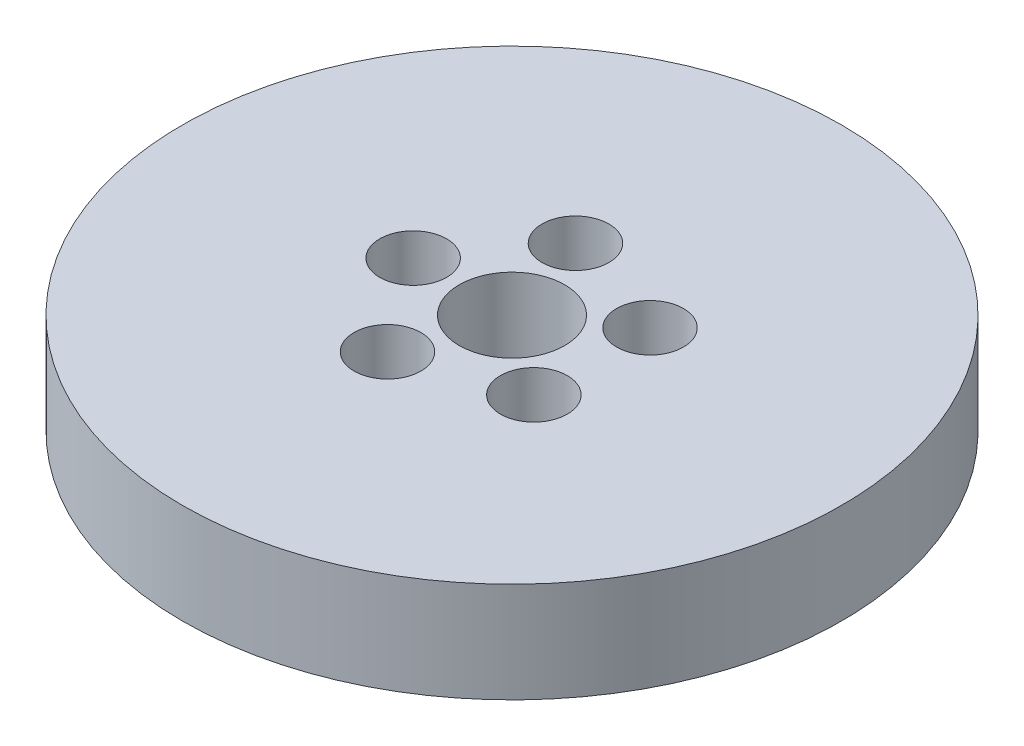
SolidWorks part; units mm, degrees
ref_plane "Front Plane" through (0, 0, 0) normal (0, 0, 1) x (1, 0, 0)
ref_plane "Top Plane" through (0, 0, 0) normal (0, 1, 0) x (1, 0, 0)
ref_plane "Right Plane" through (0, 0, 0) normal (1, 0, 0) x (0, 0, -1)
sketch "Sketch1" plane through (0, 0, 0) normal (0, 1, 0) x (1, 0, 0)
  circle A0 centre (0, 0) radius 62.5
  dimension "FLANGE_OD" = 125
extrude "Boss-Extrude1" add sketch "Sketch1" along normal blind 19
sketch "Sketch2" plane through (0, 0, 0) normal (0, 1, 0) x (1, 0, 0)
  circle A0 centre (0, 0) radius 10
  dimension "BORE_D" = 20
extrude "Cut-Extrude1" cut sketch "Sketch2" along normal through all
sketch "Sketch3" plane through (0, 19, 0) normal (0, 1, 0) x (1, 0, 0)
  circle A0 centre (0, 0) radius 18.7433 construction
  circle A1 centre (-18.7433, 0) radius 6.3404
  dimension "BOLT_D" = 12.6807
  dimension "BOLT_PCD" = 37.4865
extrude "Cut-Extrude2" cut sketch "Sketch3" against normal blind 14.7961
pattern_circular "CirPattern1" count 5 over 360 about axis through (0, 0, 0) along (0, 1, 0) of "Cut-Extrude2"
